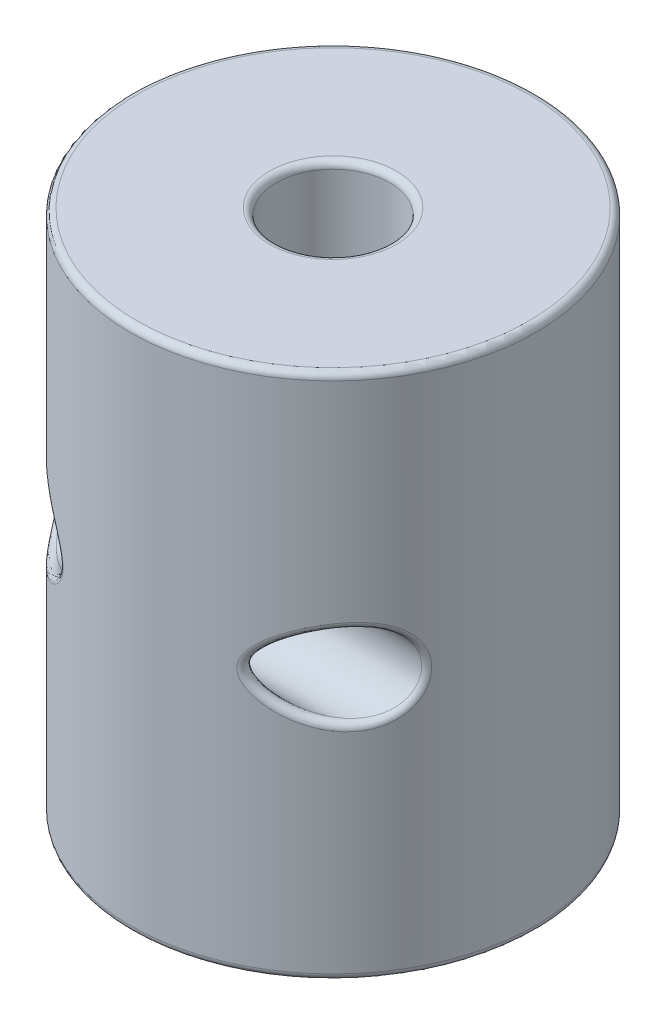
SolidWorks part; units mm, degrees
ref_plane "Front Plane" through (0, 0, 0) normal (0, 0, 1) x (1, 0, 0)
ref_plane "Top Plane" through (0, 0, 0) normal (0, 1, 0) x (1, 0, 0)
ref_plane "Right Plane" through (0, 0, 0) normal (1, 0, 0) x (0, 0, -1)
sketch "Sketch1" plane through (0, 0, 0) normal (0, 1, 0) x (1, 0, 0)
  circle A0 centre (0, 0) radius 2.1
  circle A1 centre (0, 0) radius 7.5
  dimension "D1" = 4.2
  dimension "D2" = 15
extrude "Boss-Extrude1" add sketch "Sketch1" along normal blind 19.5
sketch "Sketch2" plane through (0, 0, 0) normal (1, 0, 0) x (0, 0, -1)
  line L0 (0, 19.5) -> (0, 0) construction
  line L1 (2.1, 19.5) -> (-2.1, 19.5) construction
  line L2 (-2.1, 9.75) -> (-7.5, 9.75) construction
  line L4 (0, 14.5354) -> (-2.1, 14.5354) construction
  line L5 (-7.5, 19.5) -> (-7.5, 0) construction
  circle A0 centre (-4.8, 9.75) radius 1.5
  dimension "D2" = 3
  dimension "D1" = 2.1
extrude "Cut-Extrude1" cut sketch "Sketch2" against normal blind 19.5 and the other way blind 19.5
fillet "Fillet1" radius 0.25 6 edges at (-6.7212, 9.4619, 3.3279) (6.7212, 10.0381, 3.3279) (0, 19.5, 2.1) (0, 19.5, 7.5) (0, 0, 2.1) (0, 0, 7.5)
